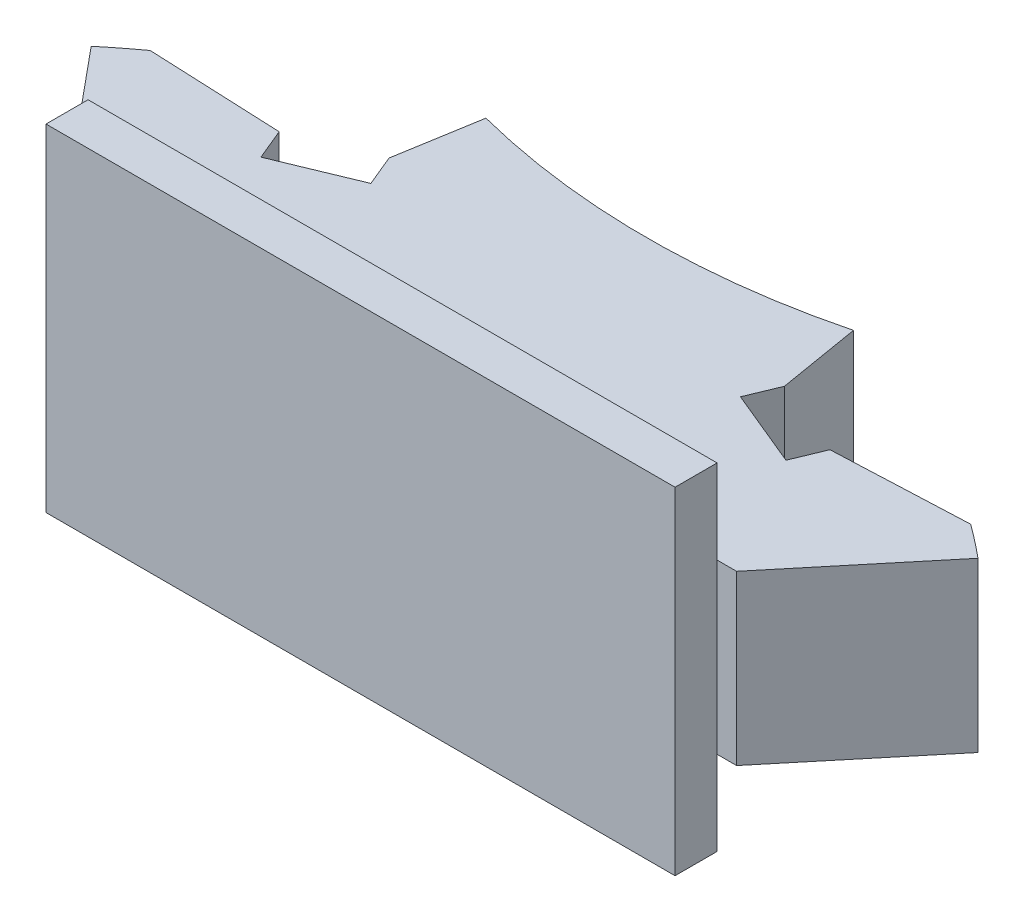
SolidWorks part; units mm, degrees
ref_plane "Front Plane" through (0, 0, 0) normal (0, 0, 1) x (1, 0, 0)
ref_plane "Top Plane" through (0, 0, 0) normal (0, 1, 0) x (1, 0, 0)
ref_plane "Right Plane" through (0, 0, 0) normal (1, 0, 0) x (0, 0, -1)
sketch "Sketch1" plane through (0, 0, 0) normal (0, 1, 0) x (1, 0, 0)
  line L0 (0, -48.8334) -> (0, 3.6176)
  line L1 (0, -48.8334) -> (20.0721, -0.375)
  line L2 (0, -48.8334) -> (-20.0721, -0.375)
  line L3 (14.9214, -4.5134) -> (20.788, -6.9434)
  line L4 (-20.788, -6.9434) -> (-14.9214, -4.5134)
  line L5 (-14.9214, -4.5134) -> (-13.8733, 1.7496)
  line L6 (-20.788, -6.9434) -> (-30.9662, -6.499)
  line L7 (14.9214, -4.5134) -> (13.8733, 1.7496)
  line L8 (20.788, -6.9434) -> (30.9662, -6.499)
  line L9 (-20.788, -6.9434) -> (-14.9214, -4.5134)
  line L10 (-20.788, -6.9434) -> (-19.816, -9.2901)
  line L11 (-14.9214, -4.5134) -> (-13.9494, -6.86)
  line L12 (-19.816, -9.2901) -> (-13.9494, -6.86)
  line L13 (14.9214, -4.5134) -> (20.788, -6.9434)
  line L14 (14.9214, -4.5134) -> (13.9494, -6.86)
  line L15 (20.788, -6.9434) -> (19.816, -9.2901)
  line L16 (13.9494, -6.86) -> (19.816, -9.2901)
  line L17 (-42.7297, -18.415) -> (42.7297, -18.415)
  line L18 (0, -48.8334) -> (22.5802, -21.59)
  line L19 (0, -48.8334) -> (-22.5802, -21.59)
  line L20 (-44.8208, -21.59) -> (-23.7417, -21.59)
  line L21 (-23.7417, -18.415) -> (-23.7417, -21.59)
  line L22 (23.7417, -18.415) -> (23.7417, -21.59)
  line L23 (-23.7417, -20.1886) -> (-33.4709, -8.4502)
  line L24 (-23.7417, -18.415) -> (23.7417, -18.415)
  line L25 (22.5802, -21.59) -> (44.8208, -21.59)
  line L26 (23.7417, -20.1886) -> (33.4709, -8.4502)
  line L27 (-23.7417, -21.59) -> (23.7417, -21.59)
  circle A0 centre (0, -48.8334) radius 52.451
  arc A1 (-13.8733, 1.7496) -> (13.8733, 1.7496) centre (0, 55.88) ccw
  point P29 (0, 0)
  point P34 (-17.4394, -6.731)
  dimension "D1" = 104.902
  dimension "D20" = 55.88
  dimension "D2" = 22.5
  dimension "D3" = 22.5
  dimension "D4" = 32
  dimension "D5" = 6.35
  dimension "D6" = 3.175
  dimension "D7" = 3.175
  dimension "D8" = 3.175
  dimension "D9" = 65
  dimension "D10" = 6.35
  dimension "D11" = 6.35
  dimension "D12" = 65
  dimension "D13" = 32
  dimension "D14" = 2.54
  dimension "D15" = 2.54
  dimension "D16" = 18.415
  dimension "D17" = 3.175
  dimension "D18" = 3.175
  dimension "D19" = 3.175
  dimension "D21" = 11.684
  dimension "D22" = 17.4394
extrude "Boss-Extrude1" add sketch "Sketch1" against normal blind 12.7 contours L0 A0 L5 L11 L12 L2 L17 | L7 A0 L0 L17 L1 L16 L14 | L18 A0 L8 L15 L16 L1 L17 | L6 A0 L19 L17 L2 L12 L10 region at (-7.4759, 0, 8.8117) region at (7.4759, 0, 8.8117) region at (22.7182, 0, 12.5283) region at (-22.7182, 0, 12.5283)
extrude "Boss-Extrude2" add sketch "Sketch1<5>" along normal blind 6.35 separate body contours L17 L21 L20 L2 | L2 L20 L0 L17 | L0 L20 L1 L17 | L22 L17 L1 L20 region at (-5.9771, 0, 19.9734) region at (5.9771, 0, 19.9734) region at (17.8358, 0, 20.032) region at (-17.8358, 0, 20.032)
sketch "Sketch1<5>" plane through (0, 0, 0) normal (0, 1, 0) x (1, 0, 0) same geometry as "Sketch1"
extrude "Boss-Extrude3" add sketch "Sketch1<6>" against normal blind 19.05 contours L17 L21 L20 L2 | L2 L20 L0 L17 | L0 L20 L1 L17 | L22 L17 L1 L20 region at (-5.9771, 0, 19.9734) region at (5.9771, 0, 19.9734) region at (17.8358, 0, 20.032) region at (-17.8358, 0, 20.032)
sketch "Sketch1<6>" plane through (0, 0, 0) normal (0, 1, 0) x (1, 0, 0) same geometry as "Sketch1"
